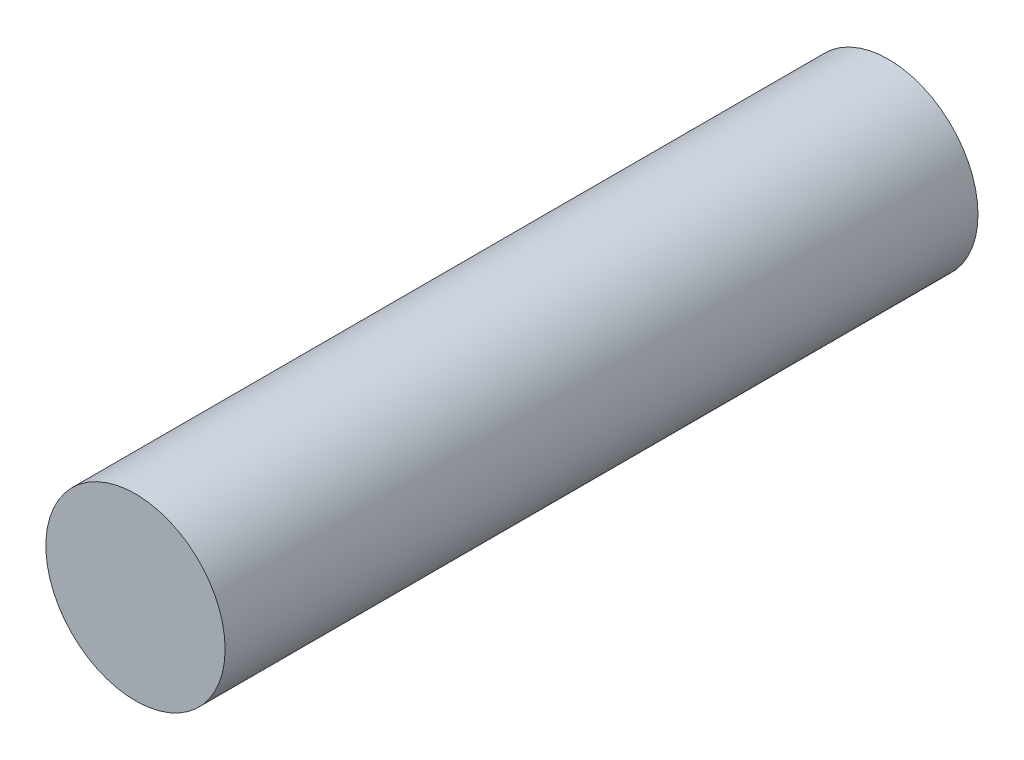
SolidWorks part; units mm, degrees
ref_plane "Front Plane" through (0, 0, 0) normal (0, 0, 1) x (1, 0, 0)
ref_plane "Top Plane" through (0, 0, 0) normal (0, 1, 0) x (1, 0, 0)
ref_plane "Right Plane" through (0, 0, 0) normal (1, 0, 0) x (0, 0, -1)
sketch "Sketch1" plane through (0, 0, 0) normal (0, 0, 1) x (1, 0, 0)
  line L1 (4.7625, 2.7496) -> (0, 5.4993)
  line L2 (0, 5.4993) -> (-4.7625, 2.7496)
  line L3 (-4.7625, 2.7496) -> (-4.7625, -2.7496)
  line L4 (-4.7625, -2.7496) -> (0, -5.4993)
  line L5 (0, -5.4993) -> (4.7625, -2.7496)
  line L6 (4.7625, -2.7496) -> (4.7625, 2.7496)
  circle A0 centre (0, 0) radius 4.7625
  point P11 (0, 0)
  dimension "D1" = 9.525
extrude "Boss-Extrude1" add sketch "Sketch1" along normal mid plane 40 contours A0 region at (0, 0, 0)
ref_axis "Axis2" through (0, 0, 0) along (0, 0, 1)
